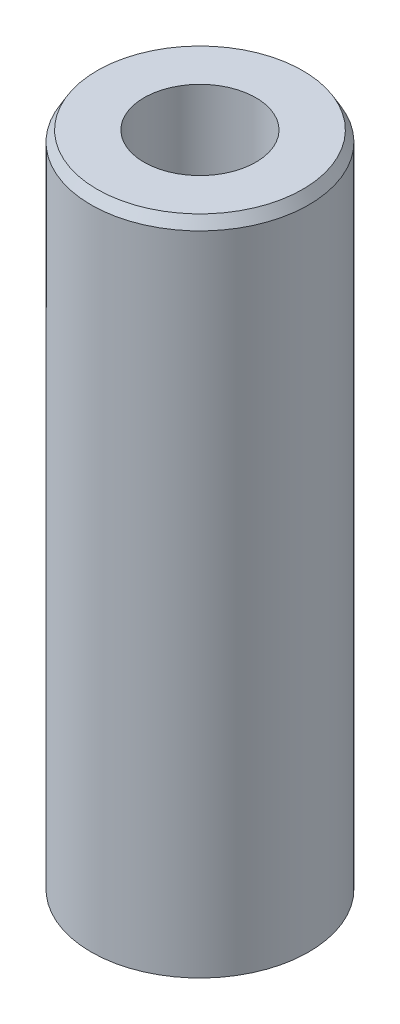
SolidWorks part; units mm, degrees
ref_plane "Front Plane" through (0, 0, 0) normal (0, 0, 1) x (1, 0, 0)
ref_plane "Top Plane" through (0, 0, 0) normal (0, 1, 0) x (1, 0, 0)
ref_plane "Right Plane" through (0, 0, 0) normal (1, 0, 0) x (0, 0, -1)
sketch "Sketch1" plane through (0, 0, 0) normal (0, 1, 0) x (1, 0, 0)
  circle A0 centre (0, 0) radius 47.5
  dimension "SHAFT_OD" = 95
extrude "Boss-Extrude1" add sketch "Sketch1" along normal blind 289.4845
sketch "Sketch2" plane through (0, 0, 0) normal (0, 1, 0) x (1, 0, 0)
  circle A0 centre (0, 0) radius 24.4
  dimension "BORE_D" = 48.8
extrude "Cut-Extrude1" cut sketch "Sketch2" along normal through all
chamfer "Chamfer1" distance 4.5631 angle 30 2 edges at (0, 289.4845, 47.5) (0, 0, 47.5) first distance on face at (0, 289.4845, 47.5) first distance on face at (0, 0, 24.4)
